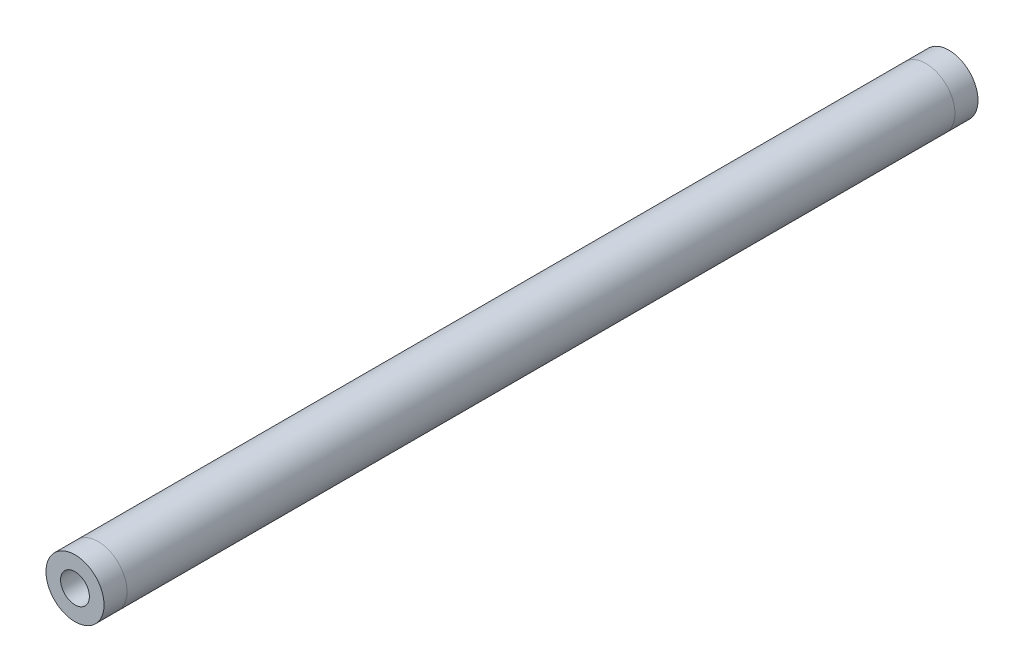
SolidWorks part; units mm, degrees
material "AISI 4130 Steel, annealed at 865C"
ref_plane "Front Plane" through (0, 0, 0) normal (0, 0, 1) x (1, 0, 0)
ref_plane "Top Plane" through (0, 0, 0) normal (0, 1, 0) x (1, 0, 0)
ref_plane "Right Plane" through (0, 0, 0) normal (1, 0, 0) x (0, 0, -1)
sketch "Axis" plane through (0, 0, 0) normal (1, 0, 0) x (0, 0, -1)
  line L0 (0, 0) -> (240.8041, 0) construction
  line L1 (240.8041, 0) -> (234.4541, 0)
  line L2 (240.8041, 0) -> (275.7291, 0) construction
  line L3 (0, 0) -> (-34.925, 0) construction
  point P4 (0, 0)
  point P5 (240.8041, 0)
  point P6 (234.4541, 0)
  point P8 (275.7291, 0)
  dimension "D1" = 6.35
  dimension "D2" = 34.925
  dimension "D3" = 34.925
sketch "Sketch1" plane through (0, 0, 0) normal (0, 0, 1) x (1, 0, 0)
  circle A0 centre (0, 0) radius 8.001
  circle A1 centre (0, 0) radius 6.477
  circle A2 centre (0, 0) radius 3.9688
  dimension "D1" = 16.002
  dimension "D2" = 1.524
  dimension "D3" = 7.9375
extrude "Threaded insert 1-1" add sketch "Sketch1" against normal blind 6.35 contours A0 A1 | A1 A2 region at (-7.7747, 0, 0) region at (-6.2938, 0, 0)
extrude "Threaded insert 1-2" add sketch "Sketch1<3>" against normal blind 9.525 from surface contours A1 A2 region at (-6.2938, 0, 0) starting at face at (8.001, 0, -6.35)
sketch "Sketch1<3>" plane through (0, 0, 0) normal (0, 0, 1) x (1, 0, 0) same geometry as "Sketch1"
extrude "Tube extrude" add sketch "Sketch1<4>" against normal up to vertex (234.4541 mm away) from surface separate body contours A0 A1 region at (-7.7747, 0, 0) up to point (0, 0, -234.4541) starting at face at (6.477, 0, -6.35)
sketch "Sketch1<4>" plane through (0, 0, 0) normal (0, 0, 1) x (1, 0, 0) same geometry as "Sketch1"
extrude "Threaded insert 2-1" add sketch "Sketch1<6>" along normal blind 9.525 from surface separate body contours A1 A2 region at (-6.2938, 0, 0) starting at face at (6.477, 0, -234.4541)
sketch "Sketch1<6>" plane through (0, 0, 0) normal (0, 0, 1) x (1, 0, 0) same geometry as "Sketch1"
extrude "Threaded insert 2-2" add sketch "Sketch1<9>" against normal blind 6.35 from surface separate body contours A1 A2 | A0 A1 region at (-7.7747, 0, 0) region at (-6.2938, 0, 0) starting at face at (6.477, 0, -234.4541)
sketch "Sketch1<9>" plane through (0, 0, 0) normal (0, 0, 1) x (1, 0, 0) same geometry as "Sketch1"
combine bodies "Combine1" operation type add bodies to combine 106 104
equation "\"Threaded insert outer thickness\"= .25"
equation "\"D1@Threaded insert 1-1\"=\"Threaded insert outer thickness\""
equation "\"D1@Threaded insert 2-2\"=\"Threaded insert outer thickness\""
equation "\"D1@Axis\" = \"Threaded insert outer thickness\""
